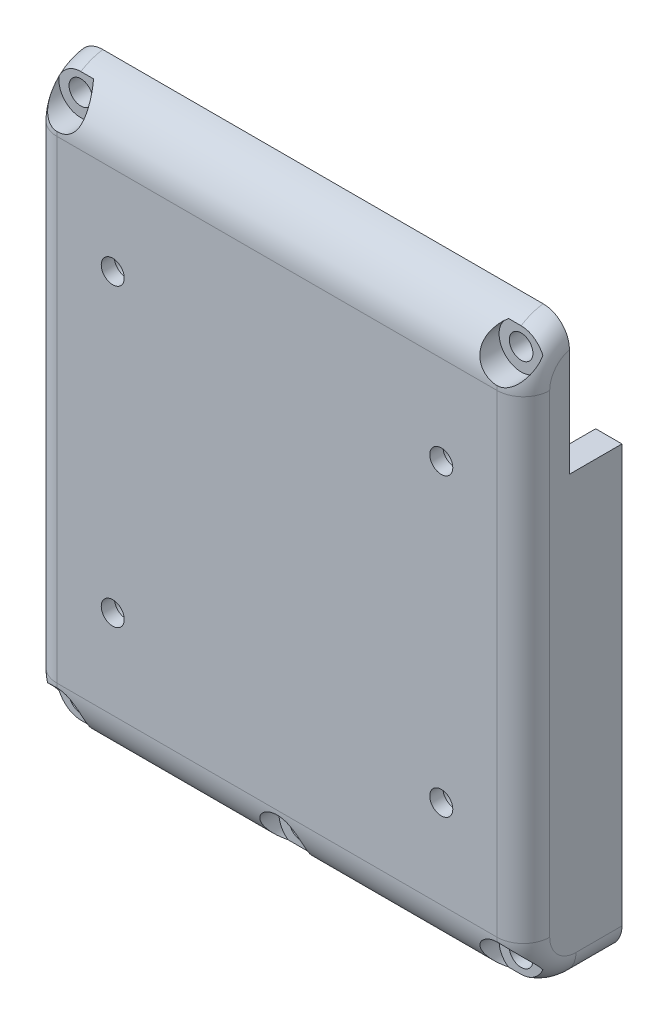
SolidWorks part; units mm, degrees
ref_plane "Front Plane" through (0, 0, 0) normal (1, 0, 0) x (0, 1, 0)
ref_plane "Top Plane" through (0, 0, 0) normal (0, 0, 1) x (0, 1, 0)
ref_plane "Right Plane" through (0, 0, 0) normal (0, 1, 0) x (-1, 0, 0)
sketch "Sketch1" plane through (0, 0, 0) normal (0, 0, 1) x (0, 1, 0)
  line L1 (-44, 37.5) -> (44, 37.5)
  line L2 (-44, 37.5) -> (-44, -37.5)
  line L3 (-44, -37.5) -> (44, -37.5)
  line L4 (44, 37.5) -> (44, -37.5)
  line L5 (-44, 37.5) -> (44, -37.5) construction
  line L6 (-44, -37.5) -> (44, 37.5) construction
  point P0 (0, 0)
  dimension "D1" = 88
  dimension "D2" = 75
extrude "Boss-Extrude1" add sketch "Sketch1" along normal blind 7
sketch "Sketch2" plane through (0, 0, 0) normal (0, 0, -1) x (1, 0, 0)
  line L1 (-37.5, -44) -> (-37.5, 44) construction
  line L2 (-37.5, 44) -> (37.5, 44)
  line L4 (37.5, 44) -> (37.5, -44) construction
  line L5 (37.5, -23.5243) -> (33.5, -23.5243)
  line L6 (33.5, -23.5243) -> (33.5, 40)
  line L7 (33.5, 40) -> (-33.5, 40)
  line L10 (37.5, 44) -> (37.5, -23.5243)
  line L11 (-37.5, 44) -> (-37.5, -23.5243)
  line L12 (-37.5, -23.5243) -> (-33.5, -23.5243)
  line L13 (-33.5, -23.5243) -> (-33.5, 40)
  line L14 (0, 40) -> (0, 44) construction
  line L16 (-37.5, -23.6243) -> (-30.65, -23.6243) construction
  arc A0 (-29.5, 40) -> (-33.5, 36) centre (-33.5, 40) cw
  arc A1 (33.5, 36) -> (29.5, 40) centre (33.5, 40) cw
  arc A2 (-4, 40) -> (4, 40) centre (0, 40) ccw
  line M13 (37.5, -44) -> (37.5, 44)
  line M14 (37.5, 44) -> (-37.5, 44)
  line M15 (-37.5, 44) -> (-37.5, -44)
  dimension "D2" = 4
  dimension "D1" = 4
  dimension "D3" = 0.1
extrude "Boss-Extrude2" add sketch "Sketch2" along normal blind 8 contours A0 L7 L13 | L7 L14 L2 L12 L13 M15 | L14 L7 L6 L5 M13 M14 | A1 L6 L7 | L7 A2 region at (-18.75, -43.2276, 0) region at (18.75, -43.2276, 0) region at (0, -38.3023, 0) region at (-31.8023, -38.3023, 0) region at (31.8023, -38.3023, 0)
fillet "Fillet3" radius 8 2 edges at (0, 44, 7) (0, -44, 7)
fillet "Fillet1" radius 4 8 edges at (37.5, -44, -4.5) (-37.5, -44, -4.5) (37.5, 0.0314, 7) (-37.5, 0.0314, 7) (37.5, 41.3542, 5) (37.5, -41.6569, 4.6569) (-37.5, 41.3542, 5) (-37.5, -41.6569, 4.6569)
sketch "Sketch4" plane through (0, 0, 7) normal (0, 0, 1) x (1, 0, 0)
  line L1 (-33.5, -40) -> (33.5, -40) construction
  line L2 (-33.5, 44) -> (-33.5, 36.0627) construction
  line L3 (33.5, 36.0627) -> (33.5, 44) construction
  line L4 (33.5, -44) -> (33.5, -36) construction
  point P0 (33.5, -40)
  point P1 (0, -40)
  point P3 (-33.5, -40)
  point P6 (-33.5, 40.0314)
  point P8 (33.5, 40.0314)
  point P23 (0, 0)
  point P26 (-33.5, 40.0314)
  point P29 (33.5, 40.0314)
  point P32 (33.5, -40)
  point P35 (0, -40)
hole_wizard "CBORE for M3 SBHCS1" positions "Sketch4" profile "Sketch5" counterbore size "M3" standard "ANSI Metric" end condition up to next
sketch "Sketch5" plane through (33.5, -40, 7) normal (1, 0, 0) x (0, -1, 0)
  line L0 (0, 0) -> (0, 15)
  line L1 (0, 15) -> (1.8, 15)
  line L3 (1.8, 15) -> (1.8, 3.65)
  line L4 (1.8, 3.65) -> (3.35, 3.65)
  line L5 (3.35, 3.65) -> (3.35, 0)
  line L7 (3.35, 0) -> (0, 0)
  line L11 (0, -6.35) -> (0, 107.95) construction
  dimension "Thru Hole Dia." = 3.6
  dimension "Thru Hole Depth" = 15
  dimension "C'Bore Dia." = 6.7
  dimension "C'Bore Depth" = 3.65
sketch "Sketch6" plane through (0, 0, 0) normal (0, 0, -1) x (1, 0, 0)
  line L0 (-12.5, 15) -> (-12.5, 38)
  line L1 (-9.5, 35) -> (9.5, 35)
  line L2 (-9.5, 35) -> (-9.5, 15)
  line L3 (-9.5, 15) -> (9.5, 15) construction
  line L4 (9.5, 35) -> (9.5, 15)
  line L5 (-9.5, 35) -> (9.5, 15) construction
  line L6 (-9.5, 15) -> (9.5, 35) construction
  line L7 (-12.5, 38) -> (12.5, 38)
  line L8 (12.5, 38) -> (12.5, 15)
  line L9 (-12.5, 15) -> (-9.5, 15)
  line L10 (9.5, 15) -> (12.5, 15)
  line L11 (0, 35) -> (0, 38) construction
  point P0 (0, 25)
  dimension "D1" = 3
  dimension "D2" = 19
  dimension "D3" = 25
  dimension "D4" = 20
extrude "Boss-Extrude3" add sketch "Sketch6" along normal up to surface (8 mm away) up to face at (31.7, -40, -8)
sketch "Sketch7" plane through (0, -15, 0) normal (0, 1, 0) x (-1, 0, 0)
  line L0 (9.5, -8) -> (-9.5, -8) construction
  line L1 (-10.05, -5) -> (10.05, -5)
  line L2 (-10.05, -5) -> (-10.05, -7)
  line L3 (-10.05, -7) -> (10.05, -7)
  line L4 (10.05, -5) -> (10.05, -7)
  line L5 (-10.05, -5) -> (10.05, -7) construction
  line L6 (-10.05, -7) -> (10.05, -5) construction
  point P0 (0, -6)
  dimension "D1" = 2
  dimension "D2" = 20.1
  dimension "D3" = 1
extrude "Cut-Extrude1" cut sketch "Sketch7" against normal up to surface (20 mm away) up to face at (0, -35, -4)
sketch "Sketch8" plane through (0, 0, 0) normal (0, 0, -1) x (1, 0, 0)
  line L1 (-9.5, 35) -> (9.5, 35)
  line L2 (-9.5, 35) -> (-9.5, -5)
  line L3 (-9.5, -5) -> (9.5, -5)
  line L4 (9.5, 35) -> (9.5, -5)
  line M22 (9.5, 15) -> (9.5, 35)
  line M23 (9.5, 35) -> (-9.5, 35)
  line M24 (-9.5, 35) -> (-9.5, 15)
  dimension "D1" = 40
extrude "Cut-Extrude2" cut sketch "Sketch8" against normal offset from surface (5 mm away) 2 contours L3 M24 M22 M23 region at (0, -15, 0) up to face at (0, 0.0314, 7)
sketch "Sketch9" plane through (0, 0, 0) normal (0, 0, -1) x (1, 0, 0)
  line L0 (-9.5, 15) -> (-9.5, -5) construction
  line L1 (-28.5, 6.5) -> (-15.5, 6.5)
  line L2 (-30, 5) -> (-30, -15)
  line L3 (-28.5, -16.5) -> (-15.5, -16.5)
  line L4 (-14, 5) -> (-14, -15)
  line L5 (-30, 6.5) -> (-14, -16.5) construction
  line L6 (-30, -16.5) -> (-14, 6.5) construction
  line L7 (-28.5, 8) -> (-15.5, 8)
  line L8 (0, 0) -> (0, 12.6026) construction
  line L9 (-31.5, -18) -> (-12.5, -18) construction
  line L10 (-31.5, 8) -> (-31.5, -18) construction
  line L16 (-12.5, 5) -> (-12.5, -15)
  line L17 (-28.5, -18) -> (-15.5, -18)
  line L18 (-31.5, 5) -> (-31.5, -15)
  line L23 (-12.5, 8) -> (-12.5, -18) construction
  line L24 (-31.5, 8) -> (-12.5, 8) construction
  line L25 (-30, 6.5) -> (-30, -16.5) construction
  line L26 (-30, -16.5) -> (-14, -16.5) construction
  line L27 (-14, 6.5) -> (-14, -16.5) construction
  line L28 (-30, 6.5) -> (-14, 6.5) construction
  line L29 (30, -16.5) -> (14, 6.5) construction
  line L30 (30, 6.5) -> (14, -16.5) construction
  line L31 (31.5, 5) -> (31.5, -15)
  line L32 (28.5, -18) -> (15.5, -18)
  line L33 (12.5, 5) -> (12.5, -15)
  line L34 (28.5, 8) -> (15.5, 8)
  line L35 (14, 5) -> (14, -15)
  line L36 (28.5, -16.5) -> (15.5, -16.5)
  line L37 (30, 5) -> (30, -15)
  line L38 (28.5, 6.5) -> (15.5, 6.5)
  arc A0 (-28.5, -18) -> (-31.5, -15) centre (-28.5, -15) cw
  arc A1 (-12.5, -15) -> (-15.5, -18) centre (-15.5, -15) cw
  arc A2 (-15.5, 8) -> (-12.5, 5) centre (-15.5, 5) cw
  arc A3 (-28.5, 8) -> (-31.5, 5) centre (-28.5, 5) ccw
  arc A4 (-30, -15) -> (-28.5, -16.5) centre (-28.5, -15) ccw
  arc A5 (-15.5, -16.5) -> (-14, -15) centre (-15.5, -15) ccw
  arc A6 (-15.5, 6.5) -> (-14, 5) centre (-15.5, 5) cw
  arc A7 (-28.5, 6.5) -> (-30, 5) centre (-28.5, 5) ccw
  arc A8 (28.5, 6.5) -> (30, 5) centre (28.5, 5) cw
  arc A9 (15.5, 6.5) -> (14, 5) centre (15.5, 5) ccw
  arc A10 (15.5, -16.5) -> (14, -15) centre (15.5, -15) cw
  arc A11 (30, -15) -> (28.5, -16.5) centre (28.5, -15) cw
  arc A12 (28.5, 8) -> (31.5, 5) centre (28.5, 5) cw
  arc A13 (15.5, 8) -> (12.5, 5) centre (15.5, 5) ccw
  arc A14 (12.5, -15) -> (15.5, -18) centre (15.5, -15) ccw
  arc A15 (28.5, -18) -> (31.5, -15) centre (28.5, -15) ccw
  point P0 (-22, -5)
  point P65 (22, -5)
  dimension "D5" = 3
  dimension "D1" = 16
  dimension "D2" = 5
  dimension "D3" = 22
  dimension "D4" = 1.5
extrude "Boss-Extrude4" add sketch "Sketch9" along normal up to surface (8 mm away) contours L7 A3 L18 A0 L17 A1 L16 A2 A7 L1 A6 L4 A5 L3 A4 L2 | L32 A15 L31 A12 L34 A13 L33 A14 L37 A11 L36 A10 L35 A9 L38 A8 region at (-22, -7.678, 0) region at (31.178, 5, 0) up to face at (0, -24.493, -8)
sketch "Sketch10" plane through (0, 0, 0) normal (0, 0, -1) x (1, 0, 0)
  line L1 (-25, 22.5) -> (25, 22.5) construction
  line L2 (-25, 22.5) -> (-25, -22.5) construction
  line L3 (-25, -22.5) -> (25, -22.5) construction
  line L4 (25, 22.5) -> (25, -22.5) construction
  line L5 (-25, 22.5) -> (25, -22.5) construction
  line L6 (-25, -22.5) -> (25, 22.5) construction
  circle A0 centre (-25, 22.5) radius 4
  circle A1 centre (25, 22.5) radius 4
  circle A2 centre (25, -22.5) radius 4
  circle A3 centre (-25, -22.5) radius 4
  point P0 (0, 0)
  dimension "D1" = 8
  dimension "D2" = 45
  dimension "D3" = 50
extrude "Boss-Extrude5" add sketch "Sketch10" along normal offset from surface (2 mm away) 9 up to face at (0, 0.0314, 7)
sketch "Sketch11" plane through (0, 0, -2) normal (0, 0, -1) x (1, 0, 0)
  circle A0 centre (-25, 22.5) radius 2.075
  circle A1 centre (25, 22.5) radius 2.075
  circle A2 centre (25, -22.5) radius 2.075
  circle A3 centre (-25, -22.5) radius 2.075
  dimension "D1" = 4.15
extrude "Cut-Extrude3" cut sketch "Sketch11" against normal blind 7 and the other way through all
sketch "Sketch13" plane through (0, 0, 5) normal (0, 0, -1) x (1, 0, 0)
  circle A0 centre (-25, 22.5) radius 1.75
  circle A1 centre (25, 22.5) radius 1.75
  circle A2 centre (25, -22.5) radius 1.75
  circle A3 centre (-25, -22.5) radius 1.75
  dimension "D1" = 3.5
extrude "Cut-Extrude4" cut sketch "Sketch13" against normal through all
fillet "Fillet2" radius 2 30 edges at (33.5, -6.2379, 0) (33.5, -36, -4) (30.6716, -37.1716, 0) (29.5, -40, -4) (16.75, -40, 0) (-29.5, -40, -4) (-33.5, -36, -4) (-16.75, -40, 0) (-30.6716, -37.1716, 0) (-33.5, -6.2379, 0) (29.5607, -6.0607, 0) (30, 5, 0) (29.5607, 16.0607, 0) (22, 16.5, 0) (14.4393, 16.0607, 0) (14, 5, 0) (14.4393, -6.0607, 0) (-29.5607, -6.0607, 0) (-30, 5, 0) (-29.5607, 16.0607, 0) (-22, 16.5, 0) (-14.4393, 16.0607, 0) (-14, 5, 0) (-14.4393, -6.0607, 0) (22, -6.5, 0) (-22, -6.5, 0) (-21, -22.5, 0) (29, -22.5, 0) (29, 22.5, 0) (-21, 22.5, 0)
